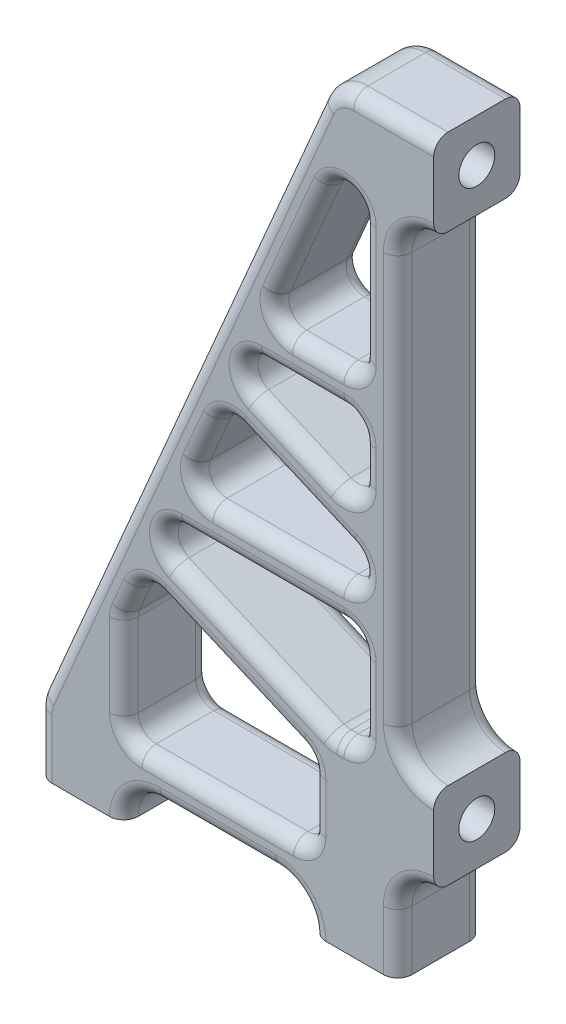
SolidWorks part; units mm, degrees
ref_plane "Спереди" through (0, 0, 0) normal (0, 0, 1) x (1, 0, 0)
ref_plane "Сверху" through (0, 0, 0) normal (0, 1, 0) x (1, 0, 0)
ref_plane "Справа" through (0, 0, 0) normal (1, 0, 0) x (0, 0, -1)
sketch "Эскиз1" plane through (0, 0, 0) normal (0, 0, 1) x (1, 0, 0)
  line L0 (-18.4277, 49) -> (76.1089, 49) construction
  line L1 (-18.4277, 9.63) -> (76.1089, 9.63) construction
  line L2 (-18.4277, 3.28) -> (76.1089, 3.28) construction
  line L3 (3, 87.6877) -> (3, -19.2431) construction
  line L4 (22.05, 87.6877) -> (22.05, -19.2431) construction
  line L5 (27.55, 46) -> (27.55, 52)
  line L6 (19.05, 0) -> (25.05, 0)
  line L7 (0, 0) -> (6, 0)
  line L8 (25.05, 0) -> (25.05, 4.13)
  line L9 (27.55, 6.63) -> (27.55, 12.63)
  line L10 (25.05, 43.5) -> (25.05, 15.13)
  line L11 (8.5, 2.5) -> (16.55, 2.5)
  line L12 (0, 0) -> (0, 4.13)
  line L13 (0.2028, 5.1163) -> (19.6818, 50.4863)
  line L14 (21.979, 52) -> (27.55, 52)
  line L15 (19.05, 6.25) -> (19.05, 11.38)
  line L16 (17.8, 5) -> (7.25, 5)
  line L17 (6, 6.25) -> (6, 12.0251)
  line L18 (6.1014, 12.5183) -> (20.1514, 45.2431)
  line L19 (20.3, 12.63) -> (21.3, 12.63)
  line L20 (22.55, 13.88) -> (22.55, 44.75)
  line L21 (28.4559, 46) -> (19.3396, 46) construction
  arc A0 (25.05, 43.5) -> (27.55, 46) centre (27.55, 43.5) cw
  arc A1 (25.05, 15.13) -> (27.55, 12.63) centre (27.55, 15.13) ccw
  arc A2 (25.05, 4.13) -> (27.55, 6.63) centre (27.55, 4.13) cw
  arc A3 (6, 0) -> (8.5, 2.5) centre (8.5, 0) cw
  arc A4 (16.55, 2.5) -> (19.05, 0) centre (16.55, 0) cw
  arc A5 (0, 4.13) -> (0.2028, 5.1163) centre (2.5, 4.13) cw
  arc A6 (19.6818, 50.4863) -> (21.979, 52) centre (21.979, 49.5) cw
  arc A7 (19.05, 6.25) -> (17.8, 5) centre (17.8, 6.25) cw
  arc A8 (7.25, 5) -> (6, 6.25) centre (7.25, 6.25) cw
  arc A9 (20.1514, 45.2431) -> (22.55, 44.75) centre (21.3, 44.75) cw
  arc A10 (6, 12.0251) -> (6.1014, 12.5183) centre (7.25, 12.0251) cw
  arc A11 (19.05, 11.38) -> (20.3, 12.63) centre (20.3, 11.38) cw
  arc A12 (21.3, 12.63) -> (22.55, 13.88) centre (21.3, 13.88) ccw
  point P13 (27.55, 49)
  point P16 (22.05, 0)
  point P19 (3, 0)
  point P31 (27.55, 9.63)
  dimension "D6" = 2.5
  dimension "D7" = 1.25
  dimension "D9" = 2.5
  dimension "D1" = 39.37
  dimension "D2" = 6.35
  dimension "D3" = 19.05
  dimension "D4" = 49
  dimension "D5" = 6
  dimension "D8" = 2.5
  dimension "D10" = 2.5
extrude "Бобышка-Вытянуть1" add sketch "Эскиз1" along normal blind 6
sketch "Эскиз2" plane through (0, 0, 0) normal (0, 0, 1) x (1, 0, 0)
  line L0 (7.4055, 15.5557) -> (19.05, 10.5563)
  line L2 (20.557, 12.63) -> (9.5404, 17.3598)
  line L5 (20.7931, 12.5286) -> (19.8069, 10.2314) construction
  line L6 (20.3, 12.63) -> (20.557, 12.63)
  line L7 (10.0335, 19.7584) -> (22.55, 19.7584)
  line L8 (7.4055, 15.5557) -> (10.2832, 22.2584)
  line L9 (10.2832, 22.2584) -> (21.3, 22.2584)
  line L10 (12.9442, 28.4563) -> (21.7931, 24.6571)
  line L11 (15.0791, 30.2603) -> (22.55, 27.0528)
  line L12 (22.55, 32.659) -> (15.5722, 32.659)
  line L13 (15.8219, 35.159) -> (22.55, 35.159)
  line L14 (22.55, 13.88) -> (22.55, 44.75) construction
  line L17 (22.55, 35.159) -> (22.55, 32.659)
  line L18 (15.8219, 35.159) -> (12.9442, 28.4563)
  line L19 (22.55, 27.0528) -> (22.55, 19.7584)
  line L21 (20.1514, 45.2431) -> (6.1014, 12.5183) construction
  line L22 (20.3, 12.63) -> (21.3, 12.63) construction
  line L23 (19.05, 11.38) -> (19.05, 10.5563)
  line L24 (19.05, 6.25) -> (19.05, 11.38) construction
  arc A1 (19.05, 11.38) -> (20.3, 12.63) centre (20.3, 11.38) cw
  arc A2 (9.5404, 17.3598) -> (10.0335, 19.7584) centre (10.0335, 18.5084) cw
  arc A3 (21.3, 22.2584) -> (21.7931, 24.6571) centre (21.3, 23.5084) ccw
  arc A4 (15.5722, 32.659) -> (15.0791, 30.2603) centre (15.5722, 31.409) ccw
  arc A6 (20.3, 12.63) -> (19.05, 11.38) centre (20.3, 11.38) ccw construction
  point P6 (20.3, 11.38)
  point P9 (20.3, 11.38)
  dimension "D2" = 1.25
  dimension "D1" = 2.5
  dimension "D3" = 2.5
  dimension "D4" = 2.5
  dimension "D5" = 2.5
extrude "Бобышка-Вытянуть2" add sketch "Эскиз2" along normal blind 6 contours L2 A2 L8 L0 | A3 L9 L8 A2 L7 L19 | A4 L18 L10 A3 L19 L11 | L13 L18 A4 L12 L17 | L17 | L2 L0 region at (13.577, 14.2884, 0) region at (18.8845, 33.8692, 0) region at (17.9609, 27.6535, 0) region at (16.1827, 21.0018, 0)
fillet "Скругление1" radius 1.25 10 edges at (19.05, 10.5563, 3) (20.557, 12.63, 3) (7.4055, 15.5557, 3) (22.55, 19.7584, 3) (10.2832, 22.2584, 3) (12.9442, 28.4563, 3) (22.55, 27.0528, 3) (22.55, 32.659, 3) (15.8219, 35.159, 3) (22.55, 35.159, 3)
sketch "Эскиз3" plane through (27.55, 0, 0) normal (1, 0, 0) x (0, 0, -1)
  line L0 (-6, 6.63) -> (0, 12.63) construction
  line L1 (0, 6.63) -> (-6, 12.63) construction
  line L2 (-6, 46) -> (0, 52) construction
  line L3 (0, 46) -> (-6, 52) construction
  circle A0 centre (-3, 49) radius 1.25
  circle A1 centre (-3, 9.63) radius 1.25
  point P12 (-3, 9.63)
  point P21 (-3, 49)
  dimension "D1" = 2.5
extrude "Вырез-Вытянуть1" cut sketch "Эскиз3" against normal blind 6 contours A1 | A0
sketch "Эскиз4" plane through (0, 0, 0) normal (0, -1, 0) x (1, 0, 0)
  line L0 (25.05, 6) -> (19.05, 0) construction
  line L1 (19.05, 6) -> (25.05, 0) construction
  line L2 (0, 6) -> (6, 0) construction
  line L3 (6, 6) -> (0, 0) construction
  circle A0 centre (3, 3) radius 1.25
  circle A1 centre (22.05, 3) radius 1.25
  point P16 (3, 3)
  point P17 (22.05, 3)
  dimension "D1" = 2.5
extrude "Вырез-Вытянуть2" cut sketch "Эскиз4" against normal blind 6
fillet "Скругление7" radius 1 98 edges at (21.5517, 45.9744, 6) (14.3478, 31.6607, 6) (18.4361, 32.659, 6) (17.943, 26.3101, 6) (22.5244, 23.2567, 6) (14.9306, 15.0456, 6) (8.8091, 18.7602, 6) (15.6668, 19.7584, 6) (25.7822, 13.3622, 6) (25.7822, 45.2678, 6) (25.7822, 5.8978, 6) (6.7322, 1.7678, 6) (18.3178, 1.7678, 6) (24.7645, 52, 6) (20.6035, 51.5875, 6) (0, 2.065, 6) (0.0512, 4.6335, 6) (19.5094, 35.159, 6) (17.943, 29.0308, 6) (16.7401, 22.2584, 6) (25.05, 29.315, 6) (25.05, 2.065, 6) (12.525, 2.5, 6) (9.9423, 27.8013, 6) (16.6751, 35.7212, 6) (18.3608, 41.0726, 6) (22.55, 40.5795, 6) (22.1839, 35.5251, 6) (22.1839, 32.2928, 6) (22.55, 30.1794, 6) (21.9878, 27.906, 6) (11.1364, 22.8207, 6) (11.7413, 25.6546, 6) (13.1361, 27.9754, 6) (16.6751, 35.7212, 0) (18.3608, 41.0726, 0) (21.5517, 45.9744, 0) (22.55, 40.5795, 0) (22.1839, 35.5251, 0) (14.3478, 31.6607, 0) (18.4361, 32.659, 0) (22.1839, 32.2928, 0) (22.55, 30.1794, 0) (21.9878, 27.906, 0) (11.1364, 22.8207, 0) (11.7413, 25.6546, 0) (13.1361, 27.9754, 0) (17.943, 26.3101, 0) (22.5244, 23.2567, 0) (20.5623, 12.6556, 0) (21.057, 12.63, 0) (22.1839, 12.9961, 0) (22.55, 16.1942, 0) (22.1839, 19.3923, 0) (15.6668, 19.7584, 0) (8.8091, 18.7602, 0) (6.3661, 5.3661, 0) (6, 9.1376, 0) (6.0256, 12.2768, 0) (6.5069, 13.4627, 0) (7.5975, 15.0749, 0) (13.4236, 12.9719, 0) (18.8438, 10.4204, 0) (19.05, 7.9913, 0) (18.6839, 5.3661, 0) (24.7645, 52, 0) (20.6035, 51.5875, 0) (0, 2.065, 0) (0.0512, 4.6335, 0) (6.7322, 1.7678, 0) (18.3178, 1.7678, 0) (25.7822, 5.8978, 0) (25.7822, 13.3622, 0) (25.7822, 45.2678, 0) (20.5623, 12.6556, 6) (21.057, 12.63, 6) (22.1839, 12.9961, 6) (22.55, 16.1942, 6) (22.1839, 19.3923, 6) (18.6839, 5.3661, 6) (12.525, 5, 6) (6.3661, 5.3661, 6) (6, 9.1376, 6) (6.0256, 12.2768, 6) (6.5069, 13.4627, 6) (7.5975, 15.0749, 6) (13.4236, 12.9719, 6) (18.8438, 10.4204, 6) (19.5094, 35.159, 0) (17.943, 29.0308, 0) (16.7401, 22.2584, 0) (14.9306, 15.0456, 0) (12.525, 5, 0) (9.9423, 27.8013, 0) (12.525, 2.5, 0) (25.05, 2.065, 0) (25.05, 29.315, 0) (19.05, 7.9913, 6)
